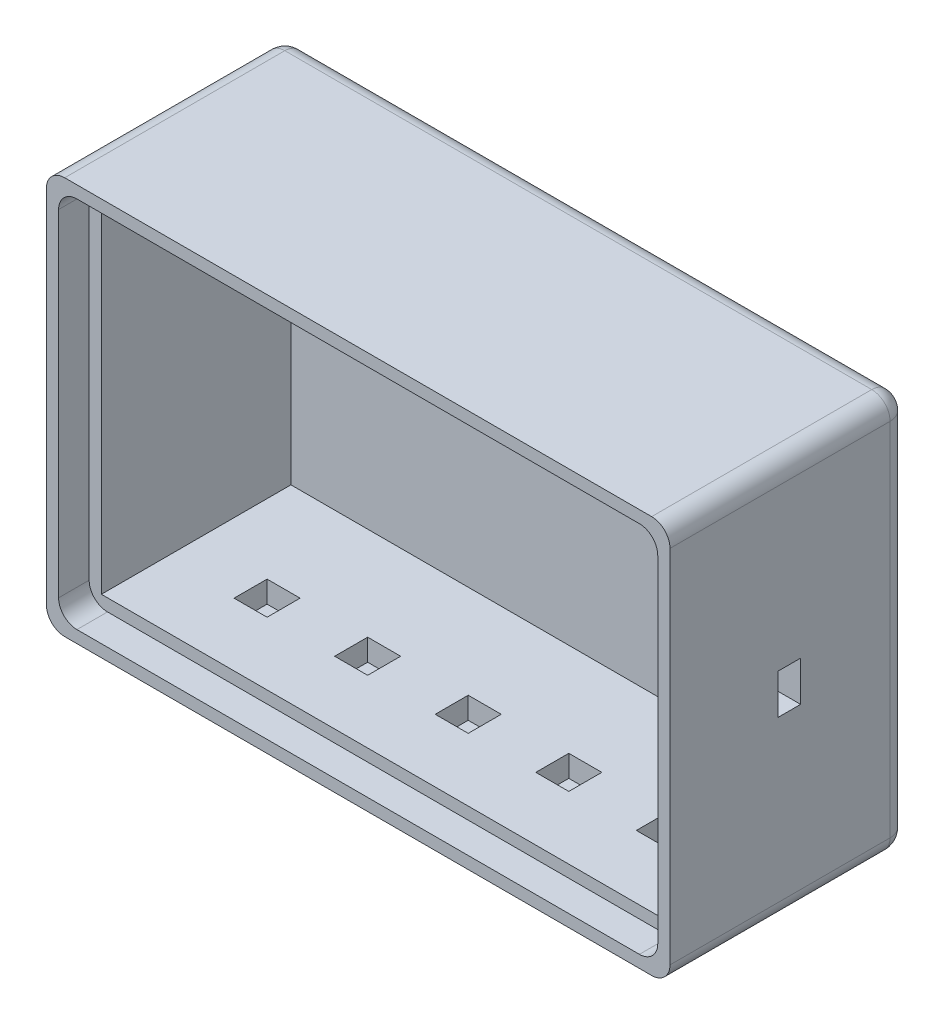
SolidWorks part; units mm, degrees
ref_plane "Přední rovina" through (0, 0, 0) normal (0, 0, 1) x (1, 0, 0)
ref_plane "Horní rovina" through (0, 0, 0) normal (0, 1, 0) x (1, 0, 0)
ref_plane "Pravá rovina" through (0, 0, 0) normal (1, 0, 0) x (0, 0, -1)
sketch "Skica1" plane through (0, 0, 0) normal (0, 0, 1) x (1, 0, 0)
  line L1 (0, 0) -> (98, 0)
  line L2 (0, 0) -> (0, 61)
  line L3 (0, 61) -> (98, 61)
  line L4 (98, 0) -> (98, 61)
  line L5 (-2, 63) -> (100, 63)
  line L6 (-2, 63) -> (-2, -2)
  line L7 (-2, -2) -> (100, -2)
  line L8 (100, 63) -> (100, -2)
  line L9 (2, 59) -> (96, 59)
  line L10 (2, 59) -> (2, 2)
  line L11 (2, 2) -> (96, 2)
  line L12 (96, 59) -> (96, 2)
  dimension "D1" = 102
  dimension "D2" = 65
  dimension "D3" = 2
  dimension "D4" = 2
  dimension "D5" = 2
  dimension "D6" = 2
  dimension "D7" = 2
  dimension "D8" = 2
  dimension "D9" = 2
  dimension "D10" = 2
  dimension "D11" = 57
  dimension "D12" = 94
extrude "Přidat vysunutím1" add sketch "Skica1" along normal blind 3 contours L6 L7 L8 L5
extrude "Přidat vysunutím2" add sketch "Skica1<4>" along normal blind 39 contours L8 L5 L6 L7 L4 L1 L2 L3 region at (49, 61.7905, 0)
sketch "Skica1<4>" plane through (0, 0, 0) normal (0, 0, 1) x (1, 0, 0) same geometry as "Skica1"
extrude "Přidat vysunutím3" add sketch "Skica1<5>" along normal blind 34 contours L1 L4 L3 L2 L9 L12 L11 L10 region at (1.1543, 30.5, 0)
sketch "Skica1<5>" plane through (0, 0, 0) normal (0, 0, 1) x (1, 0, 0) same geometry as "Skica1"
sketch "Skica2" plane through (100, 0, 0) normal (1, 0, 0) x (0, 0, -1)
  line L0 (-19.5, 63) -> (-19.5, -2) construction
  line L1 (-21.365, 27.225) -> (-17.635, 27.225)
  line L2 (-21.365, 27.225) -> (-21.365, 33.775)
  line L3 (-21.365, 33.775) -> (-17.635, 33.775)
  line L4 (-17.635, 27.225) -> (-17.635, 33.775)
  line L5 (-21.365, 27.225) -> (-17.635, 33.775) construction
  line L6 (-21.365, 33.775) -> (-17.635, 27.225) construction
  line L7 (-39, 63) -> (0, 63) construction
  line L8 (-39, -2) -> (0, -2) construction
  line L9 (-39, 30.5) -> (0, 30.5) construction
  line L10 (-39, 63) -> (-39, -2) construction
  line L11 (0, 63) -> (0, -2) construction
  point P0 (-19.5, 30.5)
  point P17 (-19.5, 30.5)
  dimension "D1" = 6.55
  dimension "D2" = 3.73
extrude "Odebrat vysunutím1" cut sketch "Skica2" against normal up to surface (4 mm away) up to face at (96, 30.5, 18.5)
fillet "Zaoblit1" radius 3 4 edges at (-2, 30.5, 0) (49, 63, 0) (100, 30.5, 0) (49, -2, 0)
sketch "Skica4" plane through (0, -2, 0) normal (0, -1, 0) x (1, 0, 0)
  line L0 (-2, 39) -> (-2, 3) construction
  line L1 (13.4, 23.7) -> (18.8, 23.7)
  line L2 (13.4, 23.7) -> (13.4, 18.3)
  line L3 (13.4, 18.3) -> (18.8, 18.3)
  line L4 (18.8, 23.7) -> (18.8, 18.3)
  line L5 (-2, 21) -> (100, 21) construction
  line L6 (100, 39) -> (100, 3) construction
  line L7 (-2, 39) -> (100, 39) construction
  line L8 (29.85, 23.7) -> (35.25, 23.7)
  line L9 (29.85, 23.7) -> (29.85, 18.3)
  line L10 (29.85, 18.3) -> (35.25, 18.3)
  line L11 (35.25, 23.7) -> (35.25, 18.3)
  line L12 (46.3, 23.7) -> (51.7, 23.7)
  line L13 (46.3, 23.7) -> (46.3, 18.3)
  line L14 (46.3, 18.3) -> (51.7, 18.3)
  line L15 (51.7, 23.7) -> (51.7, 18.3)
  line L16 (62.75, 23.7) -> (68.15, 23.7)
  line L17 (62.75, 23.7) -> (62.75, 18.3)
  line L18 (62.75, 18.3) -> (68.15, 18.3)
  line L19 (68.15, 23.7) -> (68.15, 18.3)
  line L20 (79.2, 23.7) -> (84.6, 23.7)
  line L21 (79.2, 23.7) -> (79.2, 18.3)
  line L22 (79.2, 18.3) -> (84.6, 18.3)
  line L23 (84.6, 23.7) -> (84.6, 18.3)
  line L24 (49, 39) -> (49, 3) construction
  line L25 (-2, 3) -> (100, 3) construction
  point P12 (13.4, 21)
  dimension "D1" = 5.4
  dimension "D2" = 5.4
  dimension "D4" = 5.4
  dimension "D5" = 5.4
  dimension "D6" = 5.4
  dimension "D7" = 5.4
  dimension "D8" = 11.05
  dimension "D9" = 11.05
  dimension "D10" = 11.05
  dimension "D11" = 11.05
fillet "Zaoblit2" radius 3 8 edges at (-1.1213, 62.1213, 0.8787) (99.1213, 62.1213, 0.8787) (99.1213, -1.1213, 0.8787) (-1.1213, -1.1213, 0.8787) (-2, 63, 21) (100, 63, 21) (100, -2, 21) (-2, -2, 21)
extrude "Odebrat vysunutím2" cut sketch "Skica4" against normal up to surface (4 mm away) from offset 0.45 up to face at (49, 2, 18.5) offset against normal yes
fillet "Zaoblit3" radius 3 4 edges at (98, 0, 36.5) (0, 0, 36.5) (0, 61, 36.5) (98, 61, 36.5)
